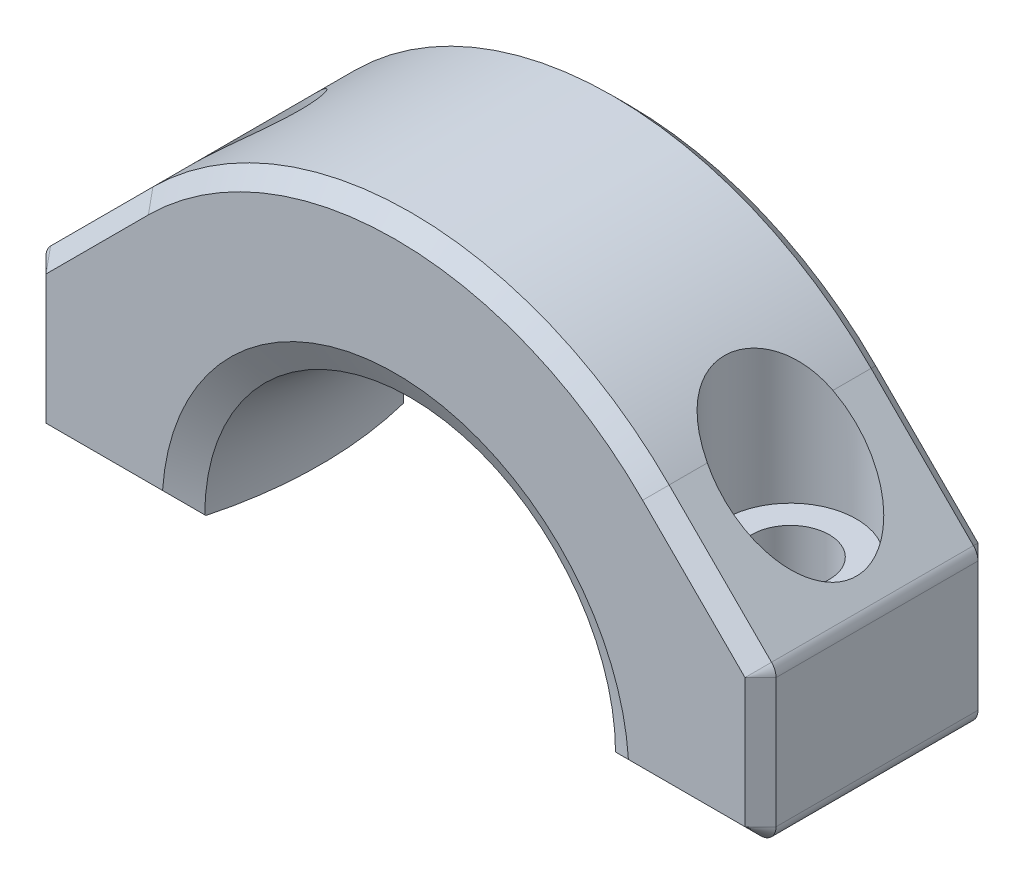
SolidWorks part; units mm, degrees
ref_plane "Front Plane" through (0, 0, 0) normal (0, 0, 1) x (1, 0, 0)
ref_plane "Top Plane" through (0, 0, 0) normal (0, 1, 0) x (1, 0, 0)
ref_plane "Right Plane" through (0, 0, 0) normal (1, 0, 0) x (0, 0, -1)
sketch "Sketch1" plane through (0, 0, 0) normal (0, 0, 1) x (1, 0, 0)
  line L0 (-13.5, 0) -> (-23.5, 0)
  line L1 (-23.5, 0) -> (-23.5, 9.734)
  line L2 (6.2559, 23.5) -> (-11.5779, 23.5) construction
  line L3 (34.9309, 0) -> (0, 0) construction
  line L4 (0, 0) -> (0, 39.8149) construction
  line L5 (0, 0) -> (-23.5, 23.5) construction
  line L6 (13.5, 0) -> (23.5, 0)
  line L8 (-16.617, 16.617) -> (-23.5, 9.734)
  line L9 (23.5, 0) -> (23.5, 9.734)
  line L10 (16.617, 16.617) -> (23.5, 9.734)
  arc A0 (13.5, 0) -> (-13.5, 0) centre (0, 0) ccw
  arc A2 (-16.617, 16.617) -> (16.617, 16.617) centre (0, 0) cw
  point P10 (0, 13.5)
  point P11 (0, 0)
  point P18 (-9.5459, 9.5459)
  point P20 (0, 23.5)
  point P22 (0, 0)
  dimension "D1" = 27
  dimension "D4" = 10
  dimension "D2" = 10
  dimension "D5" = 10
  dimension "D6" = 45
extrude "Boss-Extrude1" add sketch "Sketch1" along normal blind 15
sketch "Sketch2" plane through (0, 0, 0) normal (0, -1, 0) x (1, 0, 0)
  line L0 (0, 7.5) -> (0, 32.6089) construction
  line L1 (0, 7.5) -> (34.8135, 7.5) construction
  line L2 (-23.5, 15) -> (-23.5, 0) construction
  line L3 (-13.5, 15) -> (-13.5, 0)
  line L4 (-13.5, 15) -> (-13.5, 0) construction
  arc A0 (-13.5, 0) -> (-13.5, 15) centre (-37.3485, 7.5) ccw
  point P11 (-23.5, 7.5)
  dimension "D1" = 25
revolve "Revolve1" add sketch "Sketch2" angle 180 about L0
sketch "Sketch3" plane through (0, 0, 0) normal (0, -1, 0) x (1, 0, 0)
  line L0 (-23.5, 7.5) -> (-12.3485, 7.5) construction
  line L1 (-23.5, 15) -> (-23.5, 0) construction
  line L2 (-17.9242, 7.5) -> (-17.9242, 20.6217) construction
  line L3 (0, 0) -> (0, 26.1884) construction
  arc A0 (-13.5, 0) -> (-13.5, 15) centre (-37.3485, 7.5) ccw construction
  circle A1 centre (-17.9242, 7.5) radius 2.5
  circle A2 centre (17.9242, 7.5) radius 2.5
  dimension "D1" = 5
extrude "Cut-Extrude1" cut sketch "Sketch3" against normal through all
sketch "Sketch4" plane through (0, 0, 0) normal (0, -1, 0) x (1, 0, 0)
  line L0 (0, 0) -> (0, 23.6027) construction
  circle A0 centre (-17.9242, 7.5) radius 4.25
  circle A1 centre (17.9242, 7.5) radius 4.25
  dimension "D1" = 8.5
extrude "Cut-Extrude2" cut sketch "Sketch4" against normal through all from offset 10 offset against normal yes
fillet "Fillet1" radius 1 4 edges at (23.5, 0, 7.5) (23.5, 9.734, 7.5) (-23.5, 9.734, 7.5) (-23.5, 0, 7.5)
chamfer "Chamfer1" distance 1 angle 45 24 edges at (0, 13.5, 0) (-18, 0, 0) (-23.2071, 0.2929, 0) (-23.5, 5.1599, 0) (-23.4239, 9.7025, 0) (-19.9121, 13.322, 0) (0, 23.5, 0) (19.9121, 13.322, 0) (23.4239, 9.7025, 0) (18, 0, 0) (23.2071, 0.2929, 0) (23.5, 5.1599, 0) (0, 13.5, 15) (-18, 0, 15) (-23.2071, 0.2929, 15) (-23.5, 5.1599, 15) (-23.4239, 9.7025, 15) (-19.9121, 13.322, 15) (0, 23.5, 15) (19.9121, 13.322, 15) (23.4239, 9.7025, 15) (23.5, 5.1599, 15) (23.2071, 0.2929, 15) (18, 0, 15)
